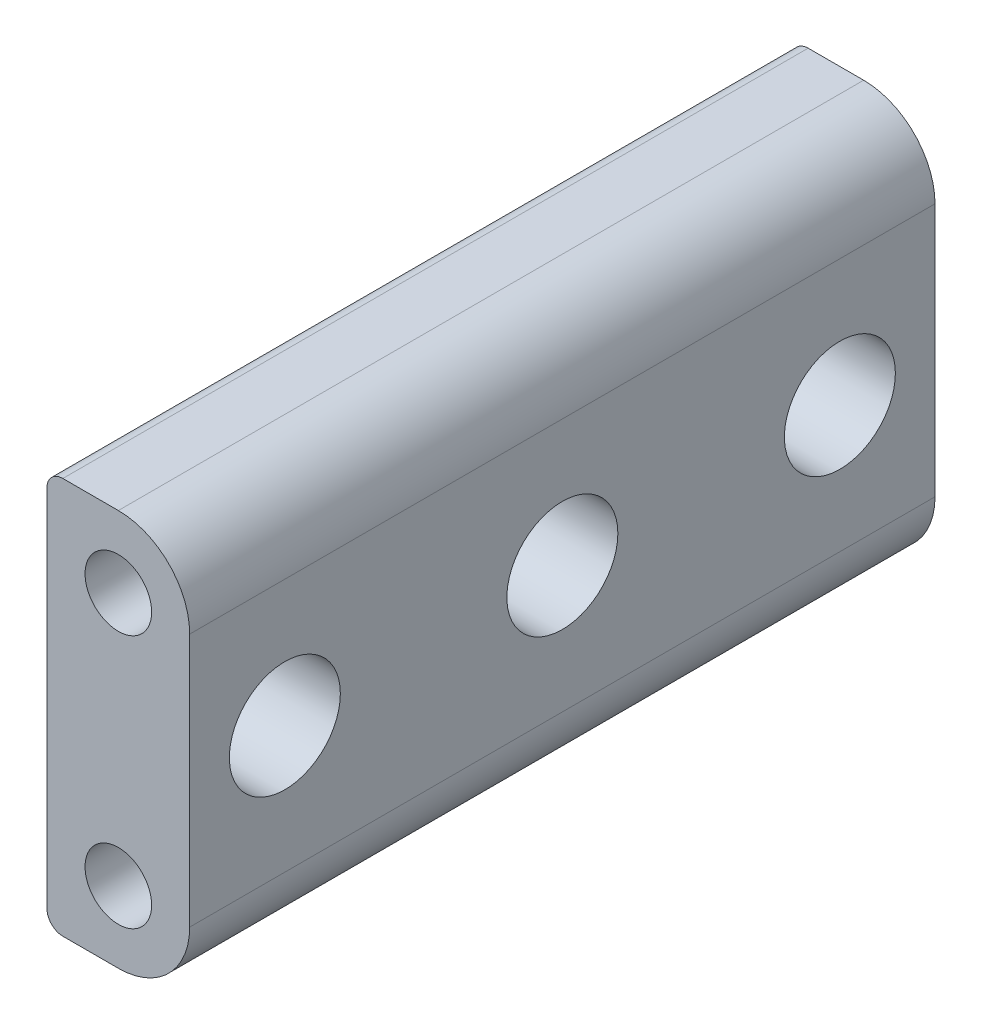
SolidWorks part; units mm, degrees
ref_plane "Front Plane" through (0, 0, 0) normal (0, 0, 1) x (1, 0, 0)
ref_plane "Top Plane" through (0, 0, 0) normal (0, 1, 0) x (1, 0, 0)
ref_plane "Right Plane" through (0, 0, 0) normal (1, 0, 0) x (0, 0, -1)
sketch "Sketch1" plane through (0, 0, 0) normal (0, 0, 1) x (1, 0, 0)
  line L0 (0, 0) -> (0, 16) construction
  line L1 (-4.5, -4.5) -> (-4.5, 20.5)
  line L2 (4.5, 0) -> (4.5, 16)
  line L5 (0, 20.5) -> (-4.5, 20.5)
  line L6 (0, -4.5) -> (-4.5, -4.5)
  arc A0 (0, -4.5) -> (4.5, 0) centre (0, 0) ccw
  arc A2 (0, 20.5) -> (4.5, 16) centre (0, 16) cw
  point P3 (0, 8)
  point P4 (0, 8)
  point P5 (-4.5, -4.213)
  dimension "D1" = 4.5
  dimension "D2" = 16
extrude "Boss-Extrude1" add sketch "Sketch1" along normal blind 47
sketch "Sketch2" plane through (0, 0, 47) normal (0, 0, 1) x (1, 0, 0)
  circle A0 centre (0, 16) radius 2.1
  circle A1 centre (0, 0) radius 2.1
  point P6 (0, 16)
  dimension "D1" = 4.2
extrude "Cut-Extrude1" cut sketch "Sketch2" against normal blind 4
sketch "Sketch3" plane through (0, 0, 0) normal (0, 0, -1) x (-1, 0, 0)
  circle A1 centre (0, 0) radius 2.1
  circle A2 centre (0, 0) radius 2.1
  circle A3 centre (0, 16) radius 2.1
  circle A4 centre (0, 16) radius 2.1
  dimension "D1" = 0
  dimension "D2" = 0
extrude "Cut-Extrude2" cut sketch "Sketch3" against normal blind 4
sketch "Sketch4" plane through (4.5, 0, 0) normal (1, 0, 0) x (0, 0, -1)
  line L0 (-47, 8) -> (0, 8) construction
  line L1 (-47, 0) -> (-47, 16) construction
  line L2 (0, 0) -> (0, 16) construction
  line L3 (0, 8) -> (-23.5, 20.5) construction
  line L5 (-23.5, 20.5) -> (-23.5, 8) construction
  line L6 (-47, 20.5) -> (0, 20.5) construction
  circle A0 centre (-41, 8) radius 3.5
  circle A1 centre (-23.5, 8) radius 3.5
  circle A2 centre (-6, 8) radius 3.5
  point P8 (-23.5, 20.5)
  dimension "D2" = 7
  dimension "D1" = 35
extrude "Cut-Extrude3" cut sketch "Sketch4" against normal blind 5
fillet "Fillet1" radius 1 2 edges at (-4.5, -4.5, 23.5) (-4.5, 20.5, 23.5)
